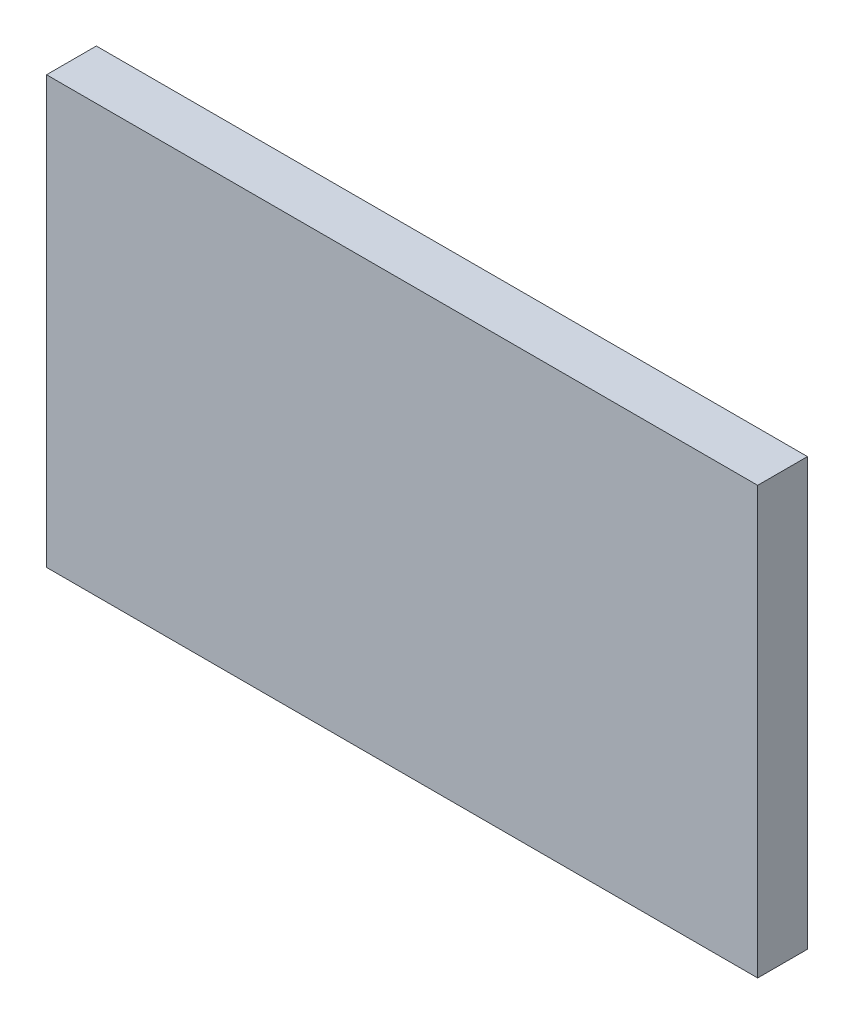
SolidWorks part; units mm, degrees
ref_plane "Front Plane" through (0, 0, 0) normal (0, 0, 1) x (1, 0, 0)
ref_plane "Top Plane" through (0, 0, 0) normal (0, 1, 0) x (1, 0, 0)
ref_plane "Right Plane" through (0, 0, 0) normal (1, 0, 0) x (0, 0, -1)
sketch "Sketch1" plane through (0, 0, 0) normal (0, 0, 1) x (1, 0, 0)
  line L1 (-50, -30) -> (50, -30)
  line L2 (-50, -30) -> (-50, 30)
  line L3 (-50, 30) -> (50, 30)
  line L4 (50, -30) -> (50, 30)
  line L5 (-50, -30) -> (50, 30) construction
  line L6 (-50, 30) -> (50, -30) construction
  point P0 (0, 0)
  point P5 (0, 0)
  dimension "D1" = 100
  dimension "D2" = 60
extrude "Boss-Extrude1" add sketch "Sketch1" along normal blind 10
extrude "Cut-Extrude1" cut sketch "Sketch1<2>" along normal blind 3
sketch "Sketch1<2>" plane through (0, 0, 0) normal (0, 0, 1) x (1, 0, 0) same geometry as "Sketch1"
sketch "Sketch2" plane through (0, 0, 0) normal (0, 0, 1) x (1, 0, 0)
  line L0 (-50, 30) -> (-10, 30)
  point P2 (0, 0)
  point P6 (-5.3254, 34.2269)
  dimension "D1" = 40
  dimension "D2" = 10
ref_plane "Plane1" through (0, 22.5, 12.9904) normal (0, 0.866, 0.5) x (1, 0, 0)
